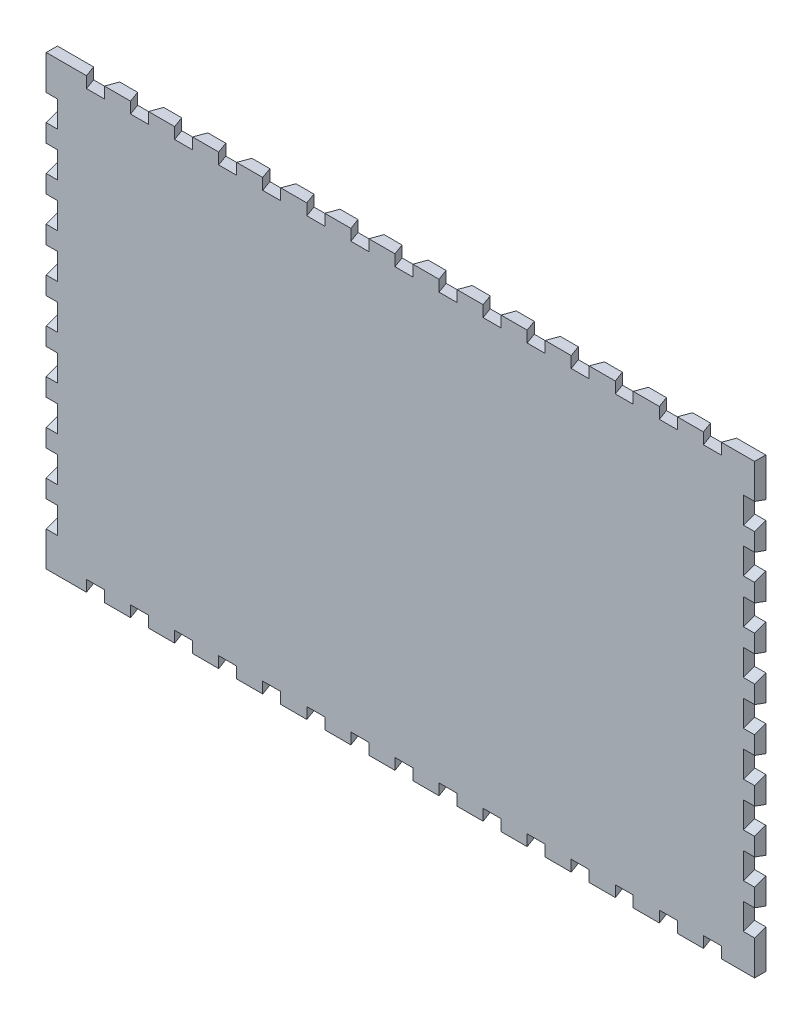
SolidWorks part; units mm, degrees
ref_plane "Front Plane" through (0, 0, 0) normal (0, 0, 1) x (1, 0, 0)
ref_plane "Top Plane" through (0, 0, 0) normal (0, 1, 0) x (1, 0, 0)
ref_plane "Right Plane" through (0, 0, 0) normal (1, 0, 0) x (0, 0, -1)
sketch "Sketch1" plane through (0, 0, 0) normal (0, 0, 1) x (1, 0, 0)
  line L1 (10, 0) -> (190, 0)
  line L56 (190, 120) -> (9.8625, 120)
  line L166 (0, 120) -> (9.8625, 120)
  line L173 (190, 120) -> (190, 0)
  line L174 (0, 120) -> (0, 0)
  line L175 (190, 60) -> (0, 60) construction
  line L176 (0, 0) -> (10, 0)
  point P5 (0, 0)
  point P8 (0, 0)
  dimension "D3" = 120
  dimension "D4" = 190
extrude "Boss-Extrude1" add sketch "Sketch1" along normal blind 3
sketch "Sketch3" plane through (0, 120, 0) normal (0, 1, 0) x (1, 0, 0)
  line L0 (190, 0) -> (0, 0) construction
  line L1 (181.0917, -3) -> (182.1836, 0)
  line L2 (175.1836, 0) -> (176.2755, -3)
  line L3 (181.0917, -3) -> (176.2755, -3)
  line L4 (182.1836, 0) -> (175.1836, 0)
  line L5 (169.2717, -3) -> (170.3636, 0)
  line L6 (170.3636, 0) -> (163.3636, 0)
  line L7 (163.3636, 0) -> (164.4555, -3)
  line L8 (169.2717, -3) -> (164.4555, -3)
  line L9 (157.4517, -3) -> (158.5436, 0)
  line L10 (158.5436, 0) -> (151.5436, 0)
  line L11 (151.5436, 0) -> (152.6355, -3)
  line L12 (157.4517, -3) -> (152.6355, -3)
  line L13 (145.6317, -3) -> (146.7236, 0)
  line L14 (146.7236, 0) -> (139.7236, 0)
  line L15 (139.7236, 0) -> (140.8155, -3)
  line L16 (145.6317, -3) -> (140.8155, -3)
  line L17 (133.8117, -3) -> (134.9036, 0)
  line L18 (134.9036, 0) -> (127.9036, 0)
  line L19 (127.9036, 0) -> (128.9955, -3)
  line L20 (133.8117, -3) -> (128.9955, -3)
  line L21 (121.9917, -3) -> (123.0836, 0)
  line L22 (123.0836, 0) -> (116.0836, 0)
  line L23 (116.0836, 0) -> (117.1755, -3)
  line L24 (121.9917, -3) -> (117.1755, -3)
  line L25 (110.1717, -3) -> (111.2636, 0)
  line L26 (111.2636, 0) -> (104.2636, 0)
  line L27 (104.2636, 0) -> (105.3555, -3)
  line L28 (110.1717, -3) -> (105.3555, -3)
  line L29 (98.3517, -3) -> (99.4436, 0)
  line L30 (99.4436, 0) -> (92.4436, 0)
  line L31 (92.4436, 0) -> (93.5355, -3)
  line L32 (98.3517, -3) -> (93.5355, -3)
  line L33 (86.5317, -3) -> (87.6236, 0)
  line L34 (87.6236, 0) -> (80.6236, 0)
  line L35 (80.6236, 0) -> (81.7155, -3)
  line L36 (86.5317, -3) -> (81.7155, -3)
  line L37 (74.7117, -3) -> (75.8036, 0)
  line L38 (75.8036, 0) -> (68.8036, 0)
  line L39 (68.8036, 0) -> (69.8955, -3)
  line L40 (74.7117, -3) -> (69.8955, -3)
  line L41 (62.8917, -3) -> (63.9836, 0)
  line L42 (63.9836, 0) -> (56.9836, 0)
  line L43 (56.9836, 0) -> (58.0755, -3)
  line L44 (62.8917, -3) -> (58.0755, -3)
  line L45 (51.0717, -3) -> (52.1636, 0)
  line L46 (52.1636, 0) -> (45.1636, 0)
  line L47 (45.1636, 0) -> (46.2555, -3)
  line L48 (51.0717, -3) -> (46.2555, -3)
  line L49 (39.2517, -3) -> (40.3436, 0)
  line L50 (40.3436, 0) -> (33.3436, 0)
  line L51 (33.3436, 0) -> (34.4355, -3)
  line L52 (39.2517, -3) -> (34.4355, -3)
  line L53 (27.4317, -3) -> (28.5236, 0)
  line L54 (28.5236, 0) -> (21.5236, 0)
  line L55 (21.5236, 0) -> (22.6155, -3)
  line L56 (27.4317, -3) -> (22.6155, -3)
  line L57 (15.6117, -3) -> (16.7036, 0)
  line L58 (16.7036, 0) -> (9.7036, 0)
  line L59 (9.7036, 0) -> (10.7955, -3)
  line L60 (15.6117, -3) -> (10.7955, -3)
  line L61 (190, -3) -> (190, 0) construction
  line L62 (232.6206, -14.8552) -> (233.7125, -11.8552)
  line L63 (226.7125, -11.8552) -> (227.8044, -14.8552)
  line L64 (232.6206, -14.8552) -> (227.8044, -14.8552)
  line L65 (233.7125, -11.8552) -> (226.7125, -11.8552)
  dimension "D1" = 15
  dimension "D2" = 7.8164
  dimension "D3" = 3
  dimension "D4" = 7
  dimension "D5" = 8.9083
  dimension "D6" = 13.7245
extrude "Cut-Extrude1" cut sketch "Sketch3" against normal blind 3
extrude "Cut-Extrude3" cut sketch "Sketch3<2>" against normal blind 187 from offset 117 offset against normal yes
sketch "Sketch3<2>" plane through (0, 120, 0) normal (0, 1, 0) x (1, 0, 0) same geometry as "Sketch3"
sketch "Sketch6" plane through (0, 0, 0) normal (-1, 0, 0) x (0, 0, 1)
  line L0 (0, 104.7919) -> (3, 103.7)
  line L1 (3, 110.7) -> (0, 109.6081)
  line L2 (0, 104.7919) -> (0, 109.6081)
  line L3 (3, 103.7) -> (3, 110.7)
  line L5 (0, 120) -> (0, 0) construction
  line L6 (0, 92.9919) -> (3, 91.9)
  line L7 (3, 91.9) -> (3, 98.9)
  line L8 (3, 98.9) -> (0, 97.8081)
  line L9 (0, 92.9919) -> (0, 97.8081)
  line L10 (0, 81.1919) -> (3, 80.1)
  line L11 (3, 80.1) -> (3, 87.1)
  line L12 (3, 87.1) -> (0, 86.0081)
  line L13 (0, 81.1919) -> (0, 86.0081)
  line L14 (0, 69.3919) -> (3, 68.3)
  line L15 (3, 68.3) -> (3, 75.3)
  line L16 (3, 75.3) -> (0, 74.2081)
  line L17 (0, 69.3919) -> (0, 74.2081)
  line L18 (0, 57.5919) -> (3, 56.5)
  line L19 (3, 56.5) -> (3, 63.5)
  line L20 (3, 63.5) -> (0, 62.4081)
  line L21 (0, 57.5919) -> (0, 62.4081)
  line L22 (0, 45.7919) -> (3, 44.7)
  line L23 (3, 44.7) -> (3, 51.7)
  line L24 (3, 51.7) -> (0, 50.6081)
  line L25 (0, 45.7919) -> (0, 50.6081)
  line L26 (0, 33.9919) -> (3, 32.9)
  line L27 (3, 32.9) -> (3, 39.9)
  line L28 (3, 39.9) -> (0, 38.8081)
  line L29 (0, 33.9919) -> (0, 38.8081)
  line L30 (0, 22.1919) -> (3, 21.1)
  line L31 (3, 21.1) -> (3, 28.1)
  line L32 (3, 28.1) -> (0, 27.0081)
  line L33 (0, 22.1919) -> (0, 27.0081)
  line L34 (0, 10.3919) -> (3, 9.3)
  line L35 (3, 9.3) -> (3, 16.3)
  line L36 (3, 16.3) -> (0, 15.2081)
  line L37 (0, 10.3919) -> (0, 15.2081)
  line L38 (3, 120) -> (0, 120) construction
  point P40 (3.2047, 107.2723)
  dimension "D2" = 3
  dimension "D3" = 7
  dimension "D4" = 4.8162
  dimension "D5" = 3
  dimension "D6" = 70
  dimension "D7" = 70
  dimension "D8" = 9.3
  dimension "D9" = 9.3
  dimension "D1" = 9
extrude "Cut-Extrude5" cut sketch "Sketch6" against normal blind 3
extrude "Cut-Extrude6" cut sketch "Sketch6<3>" against normal blind 3 from offset 187 offset against normal yes
sketch "Sketch6<3>" plane through (0, 0, 0) normal (-1, 0, 0) x (0, 0, 1) same geometry as "Sketch6"
